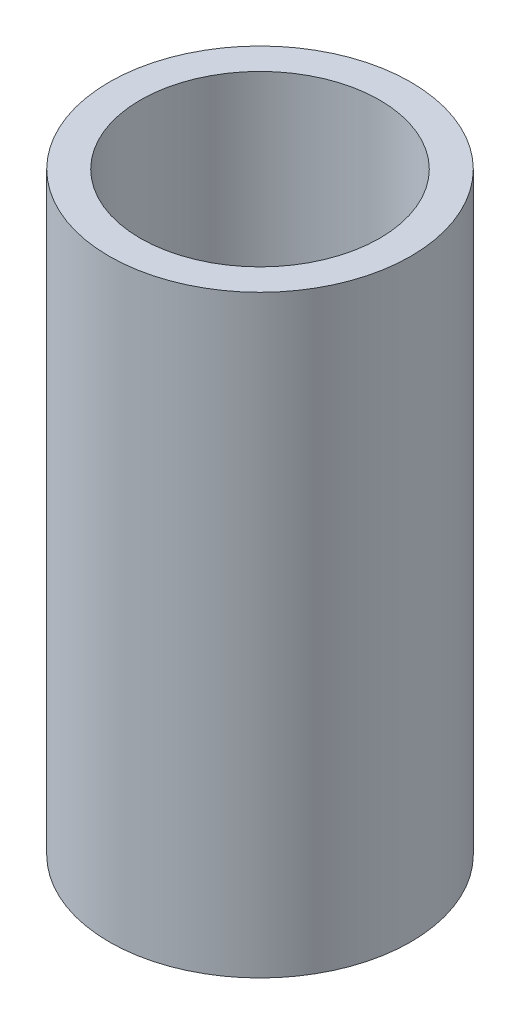
SolidWorks part; units mm, degrees
ref_plane "Front Plane" through (0, 0, 0) normal (0, 0, 1) x (1, 0, 0)
ref_plane "Top Plane" through (0, 0, 0) normal (0, 1, 0) x (1, 0, 0)
ref_plane "Right Plane" through (0, 0, 0) normal (1, 0, 0) x (0, 0, -1)
sketch "Sketch1" plane through (0, 0, 0) normal (0, 1, 0) x (1, 0, 0)
  circle A0 centre (0, 0) radius 3.175
  circle A1 centre (0, 0) radius 4
  dimension "D1" = 6.35
  dimension "D2" = 8
extrude "Boss-Extrude1" add sketch "Sketch1" along normal blind 15.748
